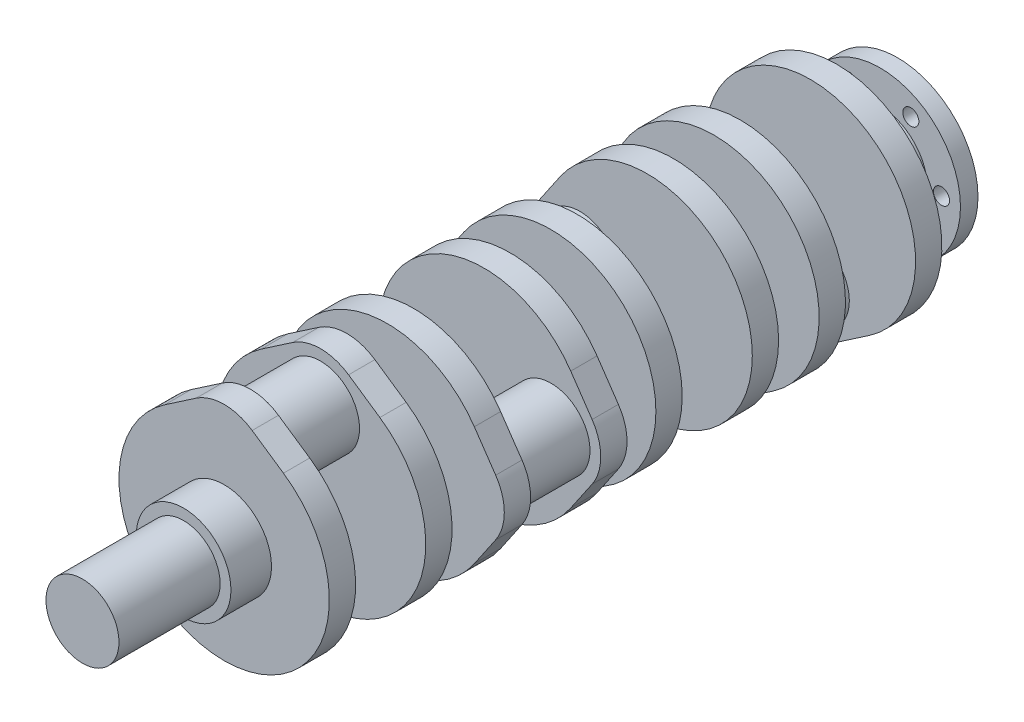
SolidWorks part; units mm, degrees
ref_plane "Front Plane" through (0, 0, 0) normal (0, 0, 1) x (1, 0, 0)
ref_plane "Top Plane" through (0, 0, 0) normal (0, 1, 0) x (1, 0, 0)
ref_plane "Right Plane" through (0, 0, 0) normal (1, 0, 0) x (0, 0, -1)
other "Configuration Table"
sketch "Sketch1" plane through (0, 0, 0) normal (0, 0, 1) x (1, 0, 0)
  circle A0 centre (0, 0) radius 32.4
extrude "Main Journal 1" add sketch "Sketch1" along normal blind 27.76 from offset 42
sketch "Sketch2" plane through (0, 0, 0) normal (0, 0, 1) x (1, 0, 0)
  circle A0 centre (0, 0) radius 32.4
extrude "Main Journal 2" add sketch "Sketch2" along normal blind 27.76 from offset 69.76 offset against normal yes
sketch "Sketch3" plane through (0, 0, 0) normal (0, 0, 1) x (1, 0, 0)
  circle A0 centre (0, 0) radius 32.4
extrude "Main Journal 3" add sketch "Sketch3" along normal blind 27.76 from offset 181.52 offset against normal yes
sketch "Sketch4" plane through (0, 0, 0) normal (0, 0, 1) x (1, 0, 0)
  circle A0 centre (0, 0) radius 32.4
extrude "Main Journal 4" add sketch "Sketch4" along normal blind 27.76 from offset 293.28 offset against normal yes
sketch "Sketch5" plane through (0, 0, 0) normal (0, 0, 1) x (1, 0, 0)
  circle A0 centre (0, 0) radius 32.4
extrude "Main Journal 5" add sketch "Sketch5" along normal blind 29.72 from offset 407 offset against normal yes
sketch "Sketch6" plane through (0, 0, 0) normal (0, 0, 1) x (1, 0, 0)
  circle A0 centre (0, 0) radius 25
extrude "Snout" add sketch "Sketch6" along normal blind 69.24 from offset 69.76
sketch "Sketch7" plane through (0, 0, 0) normal (0, 0, 1) x (1, 0, 0)
  circle A0 centre (0, 0) radius 55
extrude "Flywheel Flange" add sketch "Sketch7" along normal blind 12 from offset 419 offset against normal yes
sketch "Sketch8" plane through (0, 0, 0) normal (0, 0, 1) x (1, 0, 0)
  circle A0 centre (0, 46) radius 26.65
extrude "Rod Journal 1" add sketch "Sketch8" along normal blind 48 from offset 24 offset against normal yes
sketch "Sketch9" plane through (0, 0, 0) normal (0, 0, 1) x (1, 0, 0)
  line L0 (19.1605, 74.087) -> (40.5751, 59.4783)
  line L1 (-40.5751, 59.4783) -> (-19.1605, 74.087)
  arc A0 (-19.1605, 74.087) -> (19.1605, 74.087) centre (0, 46) cw
  arc A1 (40.5751, 59.4783) -> (-40.5751, 59.4783) centre (0, 0) cw
extrude "Web 1A" add sketch "Sketch9" along normal blind 18 from offset 24
sketch "Sketch10" plane through (0, 0, 0) normal (0, 0, 1) x (1, 0, 0)
  line L0 (19.1605, 74.087) -> (40.5751, 59.4783)
  line L1 (-40.5751, 59.4783) -> (-19.1605, 74.087)
  arc A0 (-19.1605, 74.087) -> (19.1605, 74.087) centre (0, 46) cw
  arc A1 (40.5751, 59.4783) -> (-40.5751, 59.4783) centre (0, 0) cw
extrude "Web 1B" add sketch "Sketch10" along normal blind 18 from offset 42 offset against normal yes
sketch "Sketch11" plane through (0, 0, 0) normal (0, 0, 1) x (1, 0, 0)
  circle A0 centre (46, 0) radius 26.65
extrude "Rod Journal 2" add sketch "Sketch11" along normal blind 48 from offset 135.76 offset against normal yes
sketch "Sketch12" plane through (0, 0, 0) normal (0, 0, 1) x (1, 0, 0)
  line L0 (74.087, -19.1605) -> (59.4783, -40.5751)
  line L1 (59.4783, 40.5751) -> (74.087, 19.1605)
  arc A0 (74.087, 19.1605) -> (74.087, -19.1605) centre (46, 0) cw
  arc A1 (59.4783, -40.5751) -> (59.4783, 40.5751) centre (0, 0) cw
extrude "Web 2A" add sketch "Sketch12" along normal blind 18 from offset 87.76 offset against normal yes
sketch "Sketch13" plane through (0, 0, 0) normal (0, 0, 1) x (1, 0, 0)
  line L0 (74.087, -19.1605) -> (59.4783, -40.5751)
  line L1 (59.4783, 40.5751) -> (74.087, 19.1605)
  arc A0 (74.087, 19.1605) -> (74.087, -19.1605) centre (46, 0) cw
  arc A1 (59.4783, -40.5751) -> (59.4783, 40.5751) centre (0, 0) cw
extrude "Web 2B" add sketch "Sketch13" along normal blind 18 from offset 153.76 offset against normal yes
sketch "Sketch14" plane through (0, 0, 0) normal (0, 0, 1) x (1, 0, 0)
  circle A0 centre (-46, 0) radius 26.65
extrude "Rod Journal 3" add sketch "Sketch14" along normal blind 48 from offset 247.52 offset against normal yes
sketch "Sketch15" plane through (0, 0, 0) normal (0, 0, 1) x (1, 0, 0)
  line L0 (-74.087, 19.1605) -> (-59.4783, 40.5751)
  line L1 (-59.4783, -40.5751) -> (-74.087, -19.1605)
  arc A0 (-74.087, -19.1605) -> (-74.087, 19.1605) centre (-46, 0) cw
  arc A1 (-59.4783, 40.5751) -> (-59.4783, -40.5751) centre (0, 0) cw
extrude "Web 3A" add sketch "Sketch15" along normal blind 18 from offset 199.52 offset against normal yes
sketch "Sketch16" plane through (0, 0, 0) normal (0, 0, 1) x (1, 0, 0)
  line L0 (-74.087, 19.1605) -> (-59.4783, 40.5751)
  line L1 (-59.4783, -40.5751) -> (-74.087, -19.1605)
  arc A0 (-74.087, -19.1605) -> (-74.087, 19.1605) centre (-46, 0) cw
  arc A1 (-59.4783, 40.5751) -> (-59.4783, -40.5751) centre (0, 0) cw
extrude "Web 3B" add sketch "Sketch16" along normal blind 18 from offset 265.52 offset against normal yes
sketch "Sketch17" plane through (0, 0, 0) normal (0, 0, 1) x (1, 0, 0)
  circle A0 centre (0, -46) radius 26.65
extrude "Rod Journal 4" add sketch "Sketch17" along normal blind 48 from offset 359.28 offset against normal yes
sketch "Sketch18" plane through (0, 0, 0) normal (0, 0, 1) x (1, 0, 0)
  line L0 (-19.1605, -74.087) -> (-40.5751, -59.4783)
  line L1 (40.5751, -59.4783) -> (19.1605, -74.087)
  arc A0 (19.1605, -74.087) -> (-19.1605, -74.087) centre (0, -46) cw
  arc A1 (-40.5751, -59.4783) -> (40.5751, -59.4783) centre (0, 0) cw
extrude "Web 4A" add sketch "Sketch18" along normal blind 18 from offset 311.28 offset against normal yes
sketch "Sketch19" plane through (0, 0, 0) normal (0, 0, 1) x (1, 0, 0)
  line L0 (-19.1605, -74.087) -> (-40.5751, -59.4783)
  line L1 (40.5751, -59.4783) -> (19.1605, -74.087)
  arc A0 (19.1605, -74.087) -> (-19.1605, -74.087) centre (0, -46) cw
  arc A1 (-40.5751, -59.4783) -> (40.5751, -59.4783) centre (0, 0) cw
extrude "Web 4B" add sketch "Sketch19" along normal blind 18 from offset 377.28 offset against normal yes
sketch "Sketch20" plane through (0, 0, 0) normal (0, 0, 1) x (1, 0, 0)
  circle A0 centre (42, 0) radius 5.5
  circle A1 centre (21, 36.3731) radius 5.5
  circle A2 centre (-21, 36.3731) radius 5.5
  circle A3 centre (-42, 0) radius 5.5
  circle A4 centre (-21, -36.3731) radius 5.5
  circle A5 centre (21, -36.3731) radius 5.5
extrude "Flange Bolt Holes" cut sketch "Sketch20" along normal blind 13 from offset 420 offset against normal yes
ref_axis "Main Axis" through (0, 0, -199.0801) along (0, 0, 1)
sketch3d "Pin Axis 1 Line"
  line L0 (0, 46, -20) -> (0, 46, 20)
ref_axis "Pin Axis 1" through (0, 46, -20) along (0, 0, 1)
sketch3d "Pin Axis 2 Line"
  line L0 (46, 0, -131.76) -> (46, 0, -91.76)
ref_axis "Pin Axis 2" through (46, 0, -131.76) along (0, 0, 1)
sketch3d "Pin Axis 3 Line"
  line L0 (-46, 0, -243.52) -> (-46, 0, -203.52)
ref_axis "Pin Axis 3" through (-46, 0, -243.52) along (0, 0, 1)
sketch3d "Pin Axis 4 Line"
  line L0 (0, -46, -355.28) -> (0, -46, -315.28)
ref_axis "Pin Axis 4" through (0, -46, -355.28) along (0, 0, 1)
